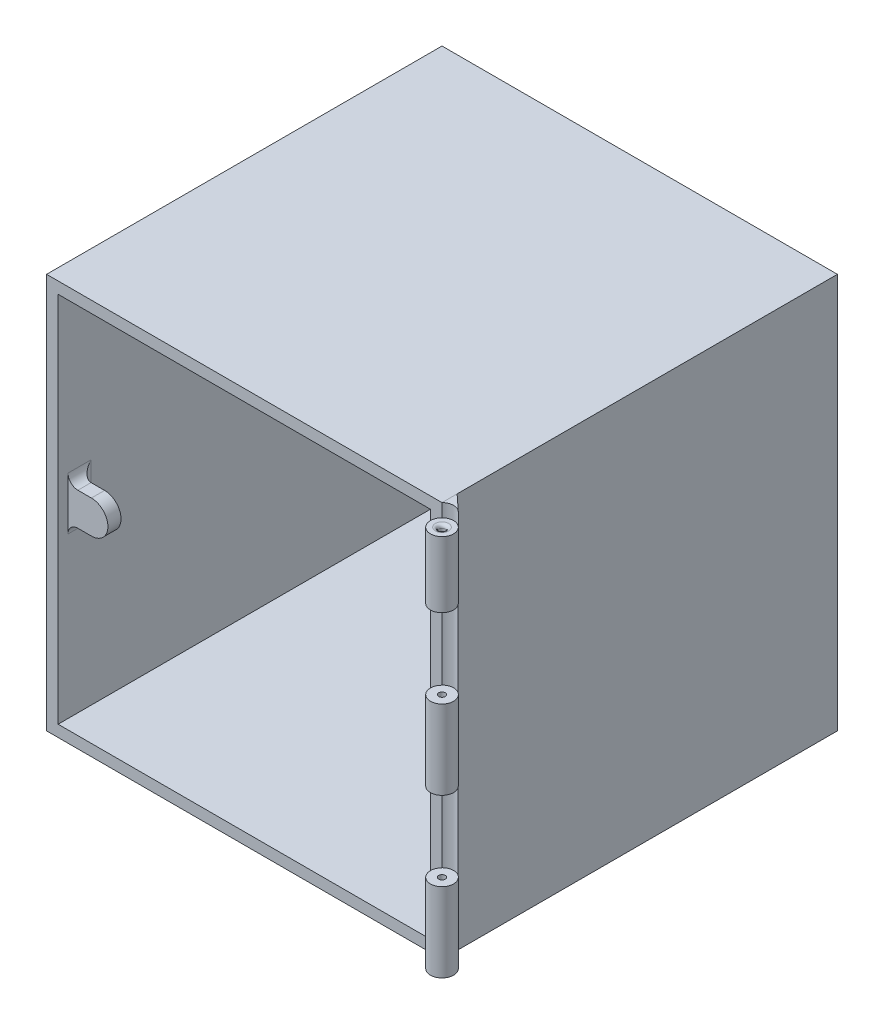
SolidWorks part; units mm, degrees
ref_plane "Plano frontal" through (0, 0, 0) normal (0, 0, 1) x (1, 0, 0)
ref_plane "Plano superior" through (0, 0, 0) normal (0, 1, 0) x (1, 0, 0)
ref_plane "Plano direito" through (0, 0, 0) normal (1, 0, 0) x (0, 0, -1)
sketch "Esboço2" plane through (0, 0, 0) normal (0, 0, 1) x (1, 0, 0)
  line L1 (-60, -60) -> (60, -60)
  line L2 (-60, -60) -> (-60, 60)
  line L3 (-60, 60) -> (60, 60)
  line L4 (60, -60) -> (60, 60)
  line L5 (-60, -60) -> (60, 60) construction
  line L6 (-60, 60) -> (60, -60) construction
  point P0 (0, 0)
extrude "Ressalto-extrusão1" add sketch "Esboço2" along normal blind 120
sketch "Esboço3" plane through (0, 0, 120) normal (0, 0, 1) x (1, 0, 0)
  line L8 (56.5, -56.5) -> (56.5, 56.5)
  line L9 (56.5, 56.5) -> (-56.5, 56.5)
  line L10 (-56.5, 56.5) -> (-56.5, -56.5)
  line L11 (-56.5, -56.5) -> (56.5, -56.5)
  line L12 (56.5, -56.5) -> (56.5, 56.5)
  line L13 (56.5, 56.5) -> (-56.5, 56.5)
  line L14 (-56.5, 56.5) -> (-56.5, -56.5)
  line L15 (-56.5, -56.5) -> (56.5, -56.5)
  dimension "D1" = 3.5
extrude "Corte-extrusão1" cut sketch "Esboço3" against normal blind 120
ref_plane "Plano1" through (0, 0, 0) normal (0, 0, 1) x (1, 0, 0)
ref_plane "Plano2" through (0, 0, 116.5) normal (0, 0, 1) x (1, 0, 0)
sketch "Esboço4" plane through (0, 0, 0) normal (0, 0, 1) x (1, 0, 0)
  line L0 (56.5, 56.5) -> (-56.5, 56.5) construction
  line L1 (-56.5, 56.5) -> (-56.5, -56.5) construction
  line L2 (-51.5, 46.5) -> (-56.5, 46.5)
  line L3 (-56.5, 46.5) -> (-56.5, 56.5)
  line L4 (-56.5, 56.5) -> (-46.5, 56.5)
  line L5 (-46.5, 56.5) -> (-46.5, 51.5)
  line L6 (0, -66) -> (0, 66) construction
  line L7 (46.5, 56.5) -> (46.5, 51.5)
  line L8 (56.5, 56.5) -> (46.5, 56.5)
  line L9 (56.5, 46.5) -> (56.5, 56.5)
  line L10 (51.5, 46.5) -> (56.5, 46.5)
  line L11 (66, 0) -> (-66, 0) construction
  line L12 (51.5, -46.5) -> (56.5, -46.5)
  line L13 (56.5, -46.5) -> (56.5, -56.5)
  line L14 (56.5, -56.5) -> (46.5, -56.5)
  line L15 (46.5, -56.5) -> (46.5, -51.5)
  line L16 (-46.5, -56.5) -> (-46.5, -51.5)
  line L17 (-56.5, -56.5) -> (-46.5, -56.5)
  line L18 (-56.5, -46.5) -> (-56.5, -56.5)
  line L19 (-51.5, -46.5) -> (-56.5, -46.5)
  line L20 (-51.5, 5) -> (-56.5, 5)
  line L21 (-56.5, 5) -> (-56.5, -5)
  line L22 (-56.5, -5) -> (-51.5, -5)
  line L23 (56.5, -5) -> (51.5, -5)
  line L24 (56.5, 5) -> (56.5, -5)
  line L25 (51.5, 5) -> (56.5, 5)
  line L26 (-5, 51.5) -> (-5, 56.5)
  line L27 (-5, 56.5) -> (5, 56.5)
  line L28 (5, 56.5) -> (5, 51.5)
  arc A0 (-51.5, 46.5) -> (-46.5, 51.5) centre (-51.5, 51.5) ccw
  arc A1 (51.5, 46.5) -> (46.5, 51.5) centre (51.5, 51.5) cw
  arc A2 (51.5, -46.5) -> (46.5, -51.5) centre (51.5, -51.5) ccw
  arc A3 (-51.5, -46.5) -> (-46.5, -51.5) centre (-51.5, -51.5) cw
  arc A4 (-51.5, -5) -> (-51.5, 5) centre (-51.5, 0) ccw
  arc A5 (51.5, -5) -> (51.5, 5) centre (51.5, 0) cw
  arc A6 (-5, 51.5) -> (5, 51.5) centre (0, 51.5) ccw
  dimension "D1" = 10
  dimension "D2" = 10
  dimension "D3" = 10
extrude "Ressalto-extrusão2" add sketch "Esboço4" along normal blind 7
sketch "Esboço6" plane through (0, 0, 0) normal (0, 1, 0) x (1, 0, 0)
  line L4 (62.4749, -122.4749) -> (65.9749, -122.4749) construction
  line L6 (62.4749, -122.4749) -> (60, -120) construction
  line L7 (60, -120) -> (60, 0) construction
  line L9 (60, -120) -> (60, -115.4138)
  line L10 (64.8176, -119.8746) -> (60, -115.4138)
  arc A0 (60, -120) -> (64.8176, -119.8746) centre (62.4749, -122.4749) ccw
  dimension "D1" = 7
  dimension "D3" = 7.0611
  dimension "D2" = 135
extrude "Ressalto-extrusão4" add sketch "Esboço6" along normal mid plane 120 separate body
ref_plane "Plano3" through (0, 36, 0) normal (0, 1, 0) x (1, 0, 0)
sketch "Esboço7" plane through (0, 36, 0) normal (0, 1, 0) x (1, 0, 0)
  circle A0 centre (62.4749, -122.4749) radius 3.55
  dimension "D1" = 7.1
extrude "Corte-extrusão2" cut sketch "Esboço7" against normal blind 24
ref_plane "Plano4" through (0, -12, 0) normal (0, 1, 0) x (1, 0, 0)
sketch "Esboço8" plane through (0, -12, 0) normal (0, 1, 0) x (1, 0, 0)
  circle A0 centre (62.4749, -122.4749) radius 3.55
  dimension "D1" = 7.1
extrude "Corte-extrusão3" cut sketch "Esboço8" against normal blind 24
sketch "Esboço5" plane through (0, 0, 116.5) normal (0, 0, 1) x (1, 0, 0)
  line L0 (-51.5, 46.5) -> (-56.5, 46.5)
  line L1 (-56.5, 46.5) -> (-56.5, 56.5)
  line L2 (-56.5, 56.5) -> (-46.5, 56.5)
  line L3 (-46.5, 56.5) -> (-46.5, 51.5)
  line L4 (46.5, 56.5) -> (46.5, 51.5)
  line L5 (56.5, 56.5) -> (46.5, 56.5)
  line L6 (56.5, 46.5) -> (56.5, 56.5)
  line L7 (51.5, 46.5) -> (56.5, 46.5)
  line L8 (51.5, -46.5) -> (56.5, -46.5)
  line L9 (56.5, -46.5) -> (56.5, -56.5)
  line L10 (56.5, -56.5) -> (46.5, -56.5)
  line L11 (46.5, -56.5) -> (46.5, -51.5)
  line L12 (-46.5, -56.5) -> (-46.5, -51.5)
  line L13 (-56.5, -56.5) -> (-46.5, -56.5)
  line L14 (-56.5, -46.5) -> (-56.5, -56.5)
  line L15 (-51.5, -46.5) -> (-56.5, -46.5)
  arc A0 (-51.5, 46.5) -> (-46.5, 51.5) centre (-51.5, 51.5) ccw
  arc A1 (51.5, 46.5) -> (46.5, 51.5) centre (51.5, 51.5) cw
  arc A2 (51.5, -46.5) -> (46.5, -51.5) centre (51.5, -51.5) ccw
  arc A3 (-51.5, -46.5) -> (-46.5, -51.5) centre (-51.5, -51.5) cw
  dimension "D1" = 10
sketch "Esboço9" plane through (0, 60, 0) normal (0, 1, 0) x (1, 0, 0)
  circle A0 centre (62.4749, -122.4749) radius 1
extrude "Corte-extrusão4" cut sketch "Esboço9" against normal blind 110
sketch "Esboço10" plane through (0, 60, 0) normal (0, 1, 0) x (1, 0, 0)
  circle A0 centre (62.4749, -122.4749) radius 3.5
extrude "Corte-extrusão5" cut sketch "Esboço10" against normal blind 4
fillet "Filete1" radius 1 1 edges at (62.4749, 56, 123.4749)
ref_plane "Plano5" through (0, 0, 117) normal (0, 0, 1) x (1, 0, 0)
sketch "Esboço11" plane through (0, 0, 117) normal (0, 0, 1) x (1, 0, 0)
  line L2 (-56.5, 56.5) -> (-56.5, -56.5) construction
  line L3 (-49.4, 5) -> (-56.5, 5)
  line L4 (-56.5, 5) -> (-56.5, -5)
  line L5 (-56.5, 5) -> (-56.5, -5) construction
  line L10 (-56.5, -5) -> (-49.4, -5)
  arc A1 (-49.4, -5) -> (-49.4, 5) centre (-49.4, 0) ccw
  dimension "D1" = 10
  dimension "D2" = 7.1
extrude "Ressalto-extrusão5" add sketch "Esboço11" against normal blind 4
fillet "Filete2" radius 3 3 edges at (-56.5, 5, 115) (-56.5, -5, 115) (-56.5, 0, 113)
sketch "Esboço13" plane through (0, 0, 0) normal (0, 0, 1) x (1, 0, 0)
  line L0 (-56.5, -56.5) -> (56.5, -56.5) construction
  line L1 (-5, -51.5) -> (-5, -56.5)
  line L2 (-5, -56.5) -> (5, -56.5)
  line L3 (5, -56.5) -> (5, -51.5)
  arc A0 (5, -51.5) -> (-5, -51.5) centre (0, -51.5) ccw
  dimension "D1" = 10
extrude "Ressalto-extrusão6" add sketch "Esboço13" along normal blind 7
